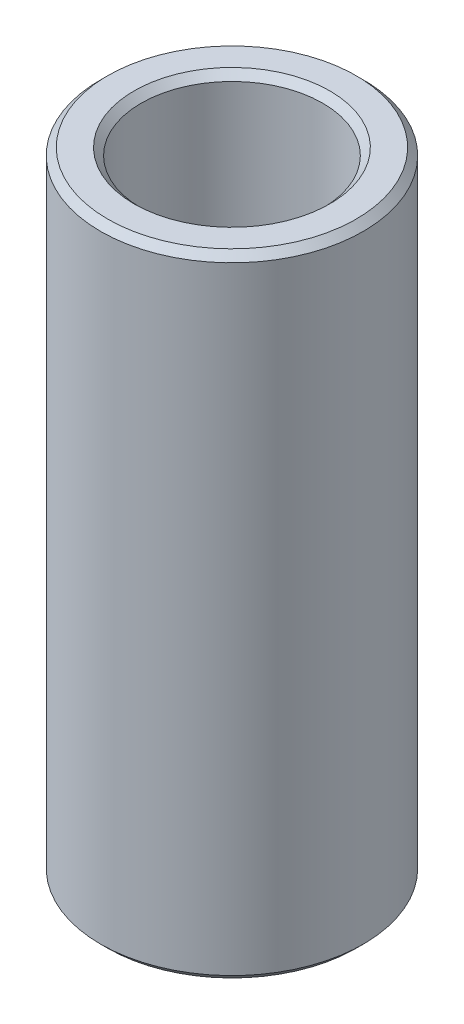
SolidWorks part; units mm, degrees
ref_plane "Front Plane" through (0, 0, 0) normal (0, 0, 1) x (1, 0, 0)
ref_plane "Top Plane" through (0, 0, 0) normal (0, 1, 0) x (1, 0, 0)
ref_plane "Right Plane" through (0, 0, 0) normal (1, 0, 0) x (0, 0, -1)
sketch "Sketch1" plane through (0, 0, 0) normal (0, 1, 0) x (1, 0, 0)
  circle A0 centre (0, 0) radius 55
  dimension "SLEEVE_OD" = 110
extrude "Boss-Extrude1" add sketch "Sketch1" along normal blind 264.4285
sketch "Sketch2" plane through (0, 0, 0) normal (0, 1, 0) x (1, 0, 0)
  circle A0 centre (0, 0) radius 38.025
  dimension "BORE_D" = 76.0501
extrude "Cut-Extrude1" cut sketch "Sketch2" along normal through all
chamfer "Chamfer1" distance 2.9731 angle 45 4 edges at (0, 264.4285, 38.025) (0, 0, 38.025) (0, 0, 55) (0, 264.4285, 55)
